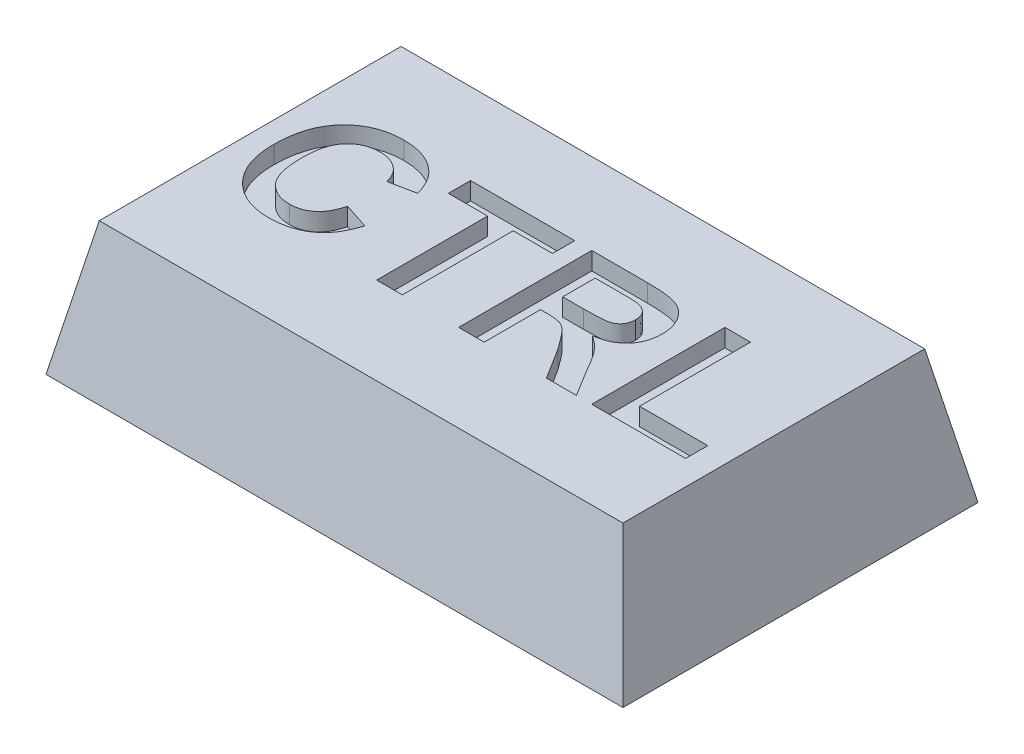
SolidWorks part; units mm, degrees
ref_plane "Front Plane" through (0, 0, 0) normal (0, 0, 1) x (1, 0, 0)
ref_plane "Top Plane" through (0, 0, 0) normal (0, 1, 0) x (1, 0, 0)
ref_plane "Right Plane" through (0, 0, 0) normal (1, 0, 0) x (0, 0, -1)
sketch "Sketch1" plane through (0, 0, 0) normal (0, 1, 0) x (1, 0, 0)
  line L1 (0, 0) -> (13, 0)
  line L2 (0, 0) -> (0, 8)
  line L3 (0, 8) -> (13, 8)
  line L4 (13, 0) -> (13, 8)
  dimension "D1" = 8
  dimension "D2" = 13
extrude "Boss-Extrude1" add sketch "Sketch1" along normal blind 3
sketch "Sketch2" plane through (0, 0, 0) normal (0, 0, 1) x (1, 0, 0)
  line L0 (0, 0) -> (0.6, 3)
  line L1 (0, 3) -> (13, 3) construction
  line L2 (0.6, 3) -> (0, 3)
  line L3 (0, 3) -> (0, 0)
  line L4 (13, 0) -> (12.4, 3)
  line L5 (12.4, 3) -> (13, 3)
  line L6 (13, 3) -> (13, 0)
  dimension "D1" = 0.6
  dimension "D2" = 0.6
extrude "Cut-Extrude1" cut sketch "Sketch2" against normal through all both and the other way through all
sketch "Sketch3" plane through (0, 0, 0) normal (1, 0, 0) x (0, 0, -1)
  line L0 (0, 0) -> (0.6, 3)
  line L1 (8, 3) -> (0, 3) construction
  line L2 (0.6, 3) -> (0, 3)
  line L3 (0, 3) -> (0, 0)
  line L4 (8, 3) -> (7.4, 3)
  line L5 (7.4, 3) -> (8, 0)
  line L6 (8, 3) -> (8, 0)
  dimension "D1" = 0.6
  dimension "D2" = 0.6
extrude "Cut-Extrude2" cut sketch "Sketch3" along normal through all both and the other way through all
sketch "Sketch4" plane through (0, 0, 0) normal (0, -1, 0) x (1, 0, 0)
  line L1 (6.5, 0) -> (6.5, -8) construction
  line L2 (13, -8) -> (0, -8) construction
  line L3 (0, 0) -> (13, 0) construction
  circle A0 centre (6.5, -3.75) radius 1.8
  dimension "D1" = 3.6
  dimension "D2" = 0
  dimension "D3" = 3.75
extrude "Cut-Extrude3" cut sketch "Sketch4" against normal blind 0.8
sketch "Sketch5" plane through (0, 0, 0) normal (0, -1, 0) x (1, 0, 0)
  line L5 (0, 0) -> (13, 0) construction
  line L6 (2.5, -8) -> (10.5, -8)
  line L7 (2.5, -8) -> (2.5, -7)
  line L8 (2.5, -7) -> (10.5, -7)
  line L9 (10.5, -8) -> (10.5, -7)
  point P2 (6.5, 0)
  dimension "D1" = 1
  dimension "D2" = 4
  dimension "D3" = 4
extrude "Boss-Extrude2" add sketch "Sketch5" along normal blind 2
fillet "Fillet1" radius 4 2 edges at (10.5, -2, -7.5) (2.5, -2, -7.5)
sketch "Sketch6" plane through (0, 3, 0) normal (0, 1, 0) x (1, 0, 0)
  text T0 "CTRL" font "Arial" height 3
extrude "Cut-Extrude4" cut sketch "Sketch6" against normal blind 0.4
